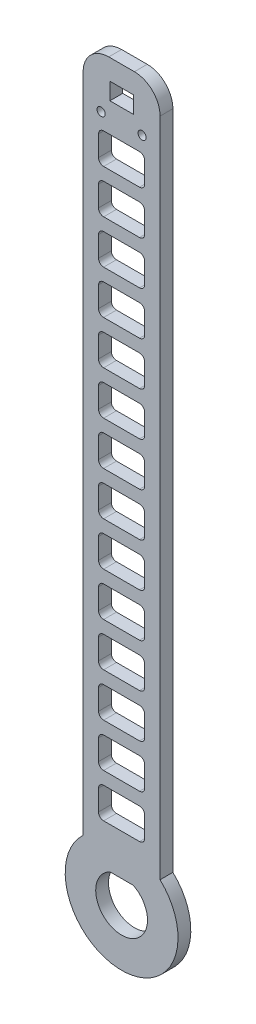
SolidWorks part; units mm, degrees
ref_plane "前视基准面" through (0, 0, 0) normal (0, 0, 1) x (1, 0, 0)
ref_plane "上视基准面" through (0, 0, 0) normal (0, 1, 0) x (1, 0, 0)
ref_plane "右视基准面" through (0, 0, 0) normal (1, 0, 0) x (0, 0, -1)
other "Configuration Table"
sketch "草图1" plane through (0, 0, 0) normal (0, 0, 1) x (1, 0, 0)
  line L1 (0, 0) -> (30, 0)
  line L2 (0, 0) -> (0, -300)
  line L3 (0, -300) -> (30, -300)
  line L4 (30, 0) -> (30, -300)
  dimension "D1" = 300
  dimension "D2" = 30
extrude "凸台-拉伸1" add sketch "草图1" along normal blind 5
sketch "草图2" plane through (0, 0, 5) normal (0, 0, 1) x (1, 0, 0)
  line L0 (0, -300) -> (30, -300) construction
  circle A0 centre (15, -284) radius 10.1
  dimension "D1" = 20.2
  dimension "D2" = 16
extrude "切除-拉伸1" cut sketch "草图2" against normal blind 10
sketch "草图3" plane through (0, 0, 5) normal (0, 0, 1) x (1, 0, 0)
  line L1 (30, 0) -> (0, 0) construction
  line L2 (10.45, -8) -> (19.55, -8)
  line L3 (10.45, -8) -> (10.45, -14.6)
  line L4 (10.45, -14.6) -> (19.55, -14.6)
  line L5 (19.55, -8) -> (19.55, -14.6)
  point P2 (15, -8)
  point P7 (15, 0)
  dimension "D2" = 6.6
  dimension "D1" = 9.1
  dimension "D3" = 0
  dimension "D4" = 8
extrude "切除-拉伸2" cut sketch "草图3" against normal blind 10
sketch "草图4" plane through (0, 0, 5) normal (0, 0, 1) x (1, 0, 0)
  line L0 (10.4163, -275) -> (19.5837, -275)
  arc A0 (19.5837, -275) -> (10.4163, -275) centre (15, -284) ccw
  dimension "D1" = 20.2
  dimension "D2" = 9
extrude "凸台-拉伸2" add sketch "草图4" against normal up to surface (5 mm away) up to face at (15, -11.3, 0)
sketch "草图5" plane through (0, 0, 0) normal (0, 0, -1) x (-1, 0, 0)
  circle A0 centre (-15, -284) radius 10.1
  circle A1 centre (-15, -284) radius 22
  dimension "D1" = 44
extrude "凸台-拉伸3" add sketch "草图5" against normal blind 5
sketch "草图6" plane through (0, 0, 5) normal (0, 0, 1) x (1, 0, 0)
  line L0 (0, 0) -> (0, -267.9065) construction
  line L1 (6, -247) -> (24, -247)
  line L2 (6, -247) -> (6, -259)
  line L3 (6, -259) -> (24, -259)
  line L4 (24, -247) -> (24, -259)
  line L5 (30, -267.9065) -> (30, 0) construction
  line L6 (6, -230) -> (6, -242)
  line L7 (6, -230) -> (24, -230)
  line L8 (24, -230) -> (24, -242)
  line L9 (6, -242) -> (24, -242)
  line L10 (6, -213) -> (6, -225)
  line L11 (6, -213) -> (24, -213)
  line L12 (24, -213) -> (24, -225)
  line L13 (6, -225) -> (24, -225)
  line L14 (6, -196) -> (6, -208)
  line L15 (6, -196) -> (24, -196)
  line L16 (24, -196) -> (24, -208)
  line L17 (6, -208) -> (24, -208)
  line L18 (6, -179) -> (6, -191)
  line L19 (6, -179) -> (24, -179)
  line L20 (24, -179) -> (24, -191)
  line L21 (6, -191) -> (24, -191)
  line L22 (6, -162) -> (6, -174)
  line L23 (6, -162) -> (24, -162)
  line L24 (24, -162) -> (24, -174)
  line L25 (6, -174) -> (24, -174)
  line L26 (6, -145) -> (6, -157)
  line L27 (6, -145) -> (24, -145)
  line L28 (24, -145) -> (24, -157)
  line L29 (6, -157) -> (24, -157)
  line L30 (6, -128) -> (6, -140)
  line L31 (6, -128) -> (24, -128)
  line L32 (24, -128) -> (24, -140)
  line L33 (6, -140) -> (24, -140)
  line L34 (6, -111) -> (6, -123)
  line L35 (6, -111) -> (24, -111)
  line L36 (24, -111) -> (24, -123)
  line L37 (6, -123) -> (24, -123)
  line L38 (6, -94) -> (6, -106)
  line L39 (6, -94) -> (24, -94)
  line L40 (24, -94) -> (24, -106)
  line L41 (6, -106) -> (24, -106)
  line L42 (6, -77) -> (6, -89)
  line L43 (6, -77) -> (24, -77)
  line L44 (24, -77) -> (24, -89)
  line L45 (6, -89) -> (24, -89)
  line L46 (6, -60) -> (6, -72)
  line L47 (6, -60) -> (24, -60)
  line L48 (24, -60) -> (24, -72)
  line L49 (6, -72) -> (24, -72)
  line L50 (6, -43) -> (6, -55)
  line L51 (6, -43) -> (24, -43)
  line L52 (24, -43) -> (24, -55)
  line L53 (6, -55) -> (24, -55)
  line L54 (6, -26) -> (6, -38)
  line L55 (6, -26) -> (24, -26)
  line L56 (24, -26) -> (24, -38)
  line L57 (6, -38) -> (24, -38)
  arc A0 (10.4163, -275) -> (19.5837, -275) centre (15, -284) ccw construction
  dimension "D1" = 6
  dimension "D2" = 6
  dimension "D3" = 25
  dimension "D4" = 12
  dimension "D5" = 14
extrude "切除-拉伸3" cut sketch "草图6" against normal blind 10
fillet "圆角2" radius 2 56 edges at (24, -38, 2.5) (6, -38, 2.5) (6, -26, 2.5) (24, -26, 2.5) (24, -55, 2.5) (6, -55, 2.5) (6, -43, 2.5) (24, -43, 2.5) (24, -72, 2.5) (6, -72, 2.5) (6, -60, 2.5) (24, -60, 2.5) (24, -89, 2.5) (6, -89, 2.5) (6, -77, 2.5) (24, -77, 2.5) (24, -106, 2.5) (6, -106, 2.5) (6, -94, 2.5) (24, -94, 2.5) (24, -123, 2.5) (6, -123, 2.5) (6, -111, 2.5) (24, -111, 2.5) (24, -140, 2.5) (6, -140, 2.5) (6, -128, 2.5) (24, -128, 2.5) (24, -157, 2.5) (6, -157, 2.5) (6, -145, 2.5) (24, -145, 2.5) (24, -174, 2.5) (6, -174, 2.5) (6, -162, 2.5) (24, -162, 2.5) (24, -191, 2.5) (6, -191, 2.5) (6, -179, 2.5) (24, -179, 2.5) (24, -208, 2.5) (6, -208, 2.5) (6, -196, 2.5) (24, -196, 2.5) (24, -225, 2.5) (6, -225, 2.5) (6, -213, 2.5) (24, -213, 2.5) (24, -242, 2.5) (6, -242, 2.5) (6, -230, 2.5) (24, -230, 2.5) (24, -247, 2.5) (24, -259, 2.5) (6, -247, 2.5) (6, -259, 2.5)
fillet "圆角1" radius 10 2 edges at (30, 0, 2.5) (0, 0, 2.5)
sketch "草图7" plane through (0, 0, 5) normal (0, 0, 1) x (1, 0, 0)
  line L0 (20, 0) -> (10, 0) construction
  line L1 (0, -10) -> (0, -267.9065) construction
  line L2 (30, -267.9065) -> (30, -10) construction
  circle A0 centre (7, -20) radius 1.6
  circle A1 centre (23, -20) radius 1.6
  dimension "D1" = 3.2
  dimension "D2" = 3.2
  dimension "D3" = 20
  dimension "D4" = 20
  dimension "D5" = 7
  dimension "D6" = 7
extrude "切除-拉伸4" cut sketch "草图7" against normal blind 10
